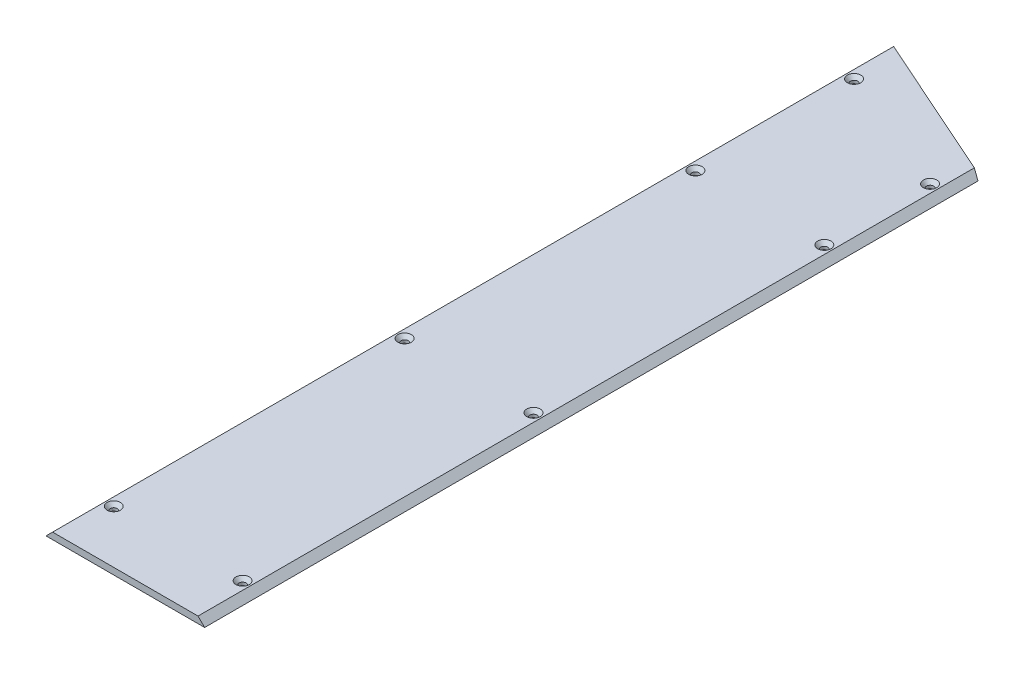
SolidWorks part; units mm, degrees
ref_plane "Front Plane" through (0, 0, 0) normal (0, 0, 1) x (1, 0, 0)
ref_plane "Top Plane" through (0, 0, 0) normal (0, 1, 0) x (1, 0, 0)
ref_plane "Right Plane" through (0, 0, 0) normal (1, 0, 0) x (0, 0, -1)
sketch "Sketch1" plane through (0, 0, 0) normal (0, 1, 0) x (1, 0, 0)
  line L1 (0, 0) -> (152.4, 0)
  line L2 (0, 0) -> (0, 1219.2)
  line L3 (0, 1219.2) -> (152.4, 1219.2)
  line L4 (152.4, 0) -> (152.4, 1219.2)
  dimension "D1" = 152.4
  dimension "D2" = 1219.2
extrude "Boss-Extrude1" add sketch "Sketch1" along normal blind 6.35
hole_wizard "CSK for 1/4 Flat Head Machine Screw1" positions "Sketch2" profile "Sketch3" countersink size "1/4" standard "ANSI Inch" end condition through all
sketch "Sketch2" plane through (0, 6.35, 0) normal (0, 1, 0) x (1, 0, 0)
  line L0 (14.2875, 1168.4) -> (14.2875, 889) construction
  line L1 (76.2, 1219.2) -> (76.2, 0) construction
  line L2 (152.4, 1219.2) -> (0, 1219.2) construction
  line L3 (0, 0) -> (152.4, 0) construction
  line L4 (0, 609.6) -> (152.4, 609.6) construction
  line L5 (0, 1219.2) -> (0, 0) construction
  line L6 (152.4, 0) -> (152.4, 1219.2) construction
  point P0 (14.2875, 1168.4)
  point P8 (138.1125, 1168.4)
  point P9 (138.1125, 889)
  point P10 (138.1125, 609.6)
  point P11 (138.1125, 330.2)
  point P12 (138.1125, 50.8)
  point P13 (14.2875, 889)
  point P14 (14.2875, 609.6)
  point P15 (14.2875, 330.2)
  point P16 (14.2875, 50.8)
  dimension "D3" = 279.4
  dimension "D4" = 14.2875
  dimension "D1" = 2
  dimension "D2" = 5
sketch "Sketch3" plane through (14.2875, 6.35, -1168.4) normal (1, 0, 0) x (0, 0, 1)
  line L0 (0, 0) -> (0, 6.35)
  line L1 (0, 6.35) -> (3.3782, 6.35)
  line L2 (3.3782, 6.35) -> (3.3782, 3.5209)
  line L3 (3.3782, 3.5209) -> (6.4389, 0)
  line L5 (6.4389, 0) -> (0, 0)
  line L6 (-3.3782, 3.5209) -> (-6.4389, 0) construction
  line L11 (0, -6.35) -> (0, 107.95) construction
  dimension "Thru Hole Dia." = 6.7564
  dimension "Thru Hole Depth" = 6.35
  dimension "Near C'Sink Dia." = 12.8778
  dimension "Near C'Sink Angle" = 82
chamfer "Chamfer1" distance 6.35 angle 45 2 edges at (0, 6.35, -609.6) (152.4, 6.35, -609.6)
sketch "Sketch4" plane through (0, 6.35, 0) normal (0, 1, 0) x (1, 0, 0)
  line L0 (152.4, 0) -> (152.4, 742.95) construction
  line L1 (152.4, 0) -> (152.4, 1219.2) construction
  line L2 (152.4, 742.95) -> (0, 810.8029)
  line L3 (0, 1219.2) -> (0, 0) construction
  line L4 (152.4, 1219.2) -> (152.4, 742.95)
  line L5 (0, 810.8029) -> (0, 1219.2)
  line L6 (0, 1219.2) -> (152.4, 1219.2)
  dimension "D1" = 742.95
  dimension "D2" = 66
extrude "Cut-Extrude1" cut sketch "Sketch4" against normal through all
hole_wizard "CSK for 1/4 Flat Head Machine Screw2" positions "Sketch5" profile "Sketch6" countersink size "1/4" standard "ANSI Inch" end condition through all
sketch "Sketch5" plane through (0, 6.35, 0) normal (0, 1, 0) x (1, 0, 0)
  line L0 (138.1125, 609.6) -> (138.1125, 749.3112) construction
  line L1 (6.35, 807.9756) -> (146.05, 745.7772) construction
  line L3 (14.2875, 609.6) -> (14.2875, 804.4416) construction
  circle A1 centre (14.2875, 609.6) radius 3.3782 construction
  point P0 (14.2875, 762)
  point P2 (138.1125, 711.2)
  dimension "D1" = 101.6
  dimension "D2" = 152.4
sketch "Sketch6" plane through (14.2875, 6.35, -762) normal (1, 0, 0) x (0, 0, 1)
  line L0 (0, 0) -> (0, 6.35)
  line L1 (0, 6.35) -> (3.3782, 6.35)
  line L2 (3.3782, 6.35) -> (3.3782, 3.5209)
  line L3 (3.3782, 3.5209) -> (6.4389, 0)
  line L5 (6.4389, 0) -> (0, 0)
  line L6 (-3.3782, 3.5209) -> (-6.4389, 0) construction
  line L11 (0, -6.35) -> (0, 107.95) construction
  dimension "Thru Hole Dia." = 6.7564
  dimension "Thru Hole Depth" = 6.35
  dimension "Near C'Sink Dia." = 12.8778
  dimension "Near C'Sink Angle" = 82
